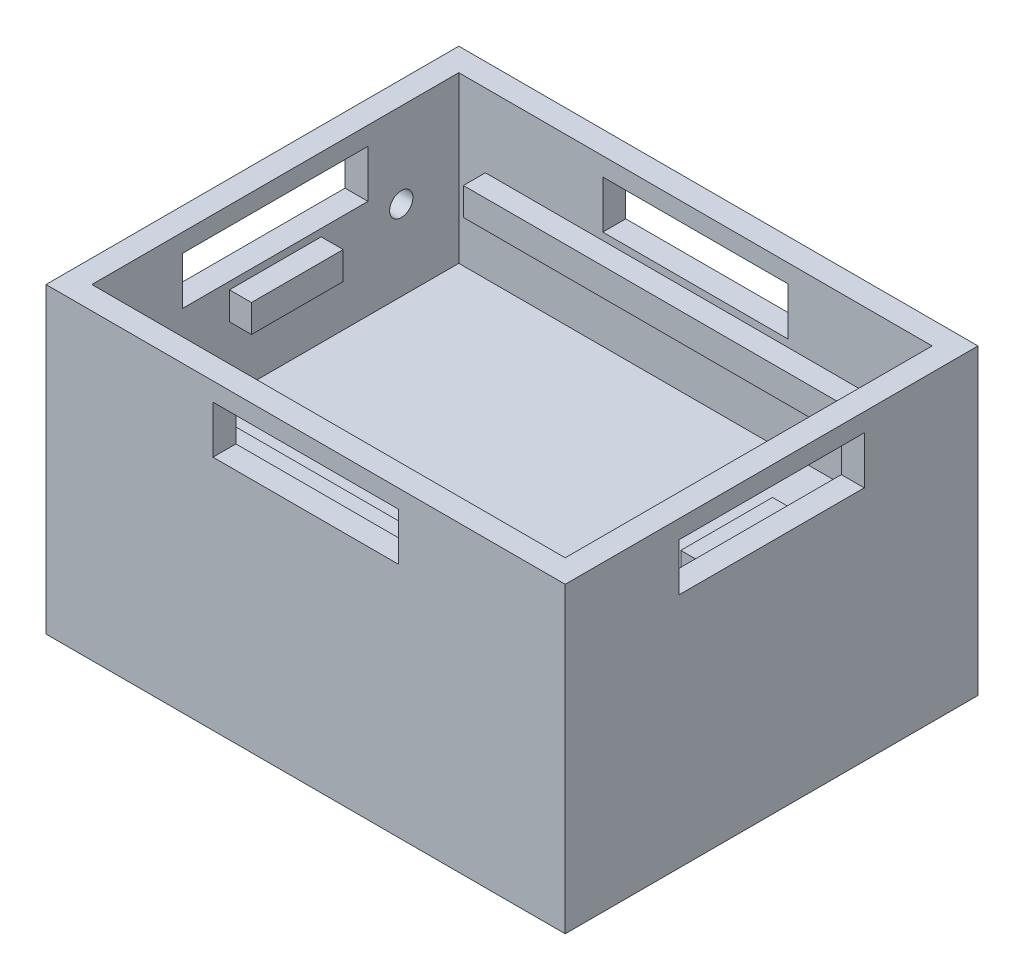
SolidWorks part; units mm, degrees
ref_plane "Front Plane" through (0, 0, 0) normal (0, 0, 1) x (1, 0, 0)
ref_plane "Top Plane" through (0, 0, 0) normal (0, 1, 0) x (1, 0, 0)
ref_plane "Right Plane" through (0, 0, 0) normal (1, 0, 0) x (0, 0, -1)
sketch "Sketch1" plane through (0, 0, 0) normal (0, 1, 0) x (1, 0, 0)
  line L0 (-2.5, 2.5) -> (-2.5, 202.5)
  line L5 (-15, -10) -> (268, -10)
  line L6 (-15, -10) -> (-15, 215)
  line L7 (-15, 215) -> (268, 215)
  line L8 (268, -10) -> (268, 215)
  line L9 (-2.5, 202.5) -> (255.5, 202.5)
  line L10 (255.5, 2.5) -> (255.5, 202.5)
  line L11 (-2.5, 2.5) -> (255.5, 2.5)
  dimension "D1" = 283
  dimension "D2" = 225
  dimension "D3" = 12.5
extrude "Walls" add sketch "Sketch1" along normal blind 90
sketch "Sketch3" plane through (0, 0, 0) normal (0, -1, 0) x (1, 0, 0)
  line L0 (268, -215) -> (-15, -215) construction
  line L1 (268, 10) -> (268, -215) construction
  line L2 (-15, 10) -> (268, 10) construction
  line L3 (-15, -215) -> (-15, 10) construction
  line L4 (268, -215) -> (-15, -215)
  line L5 (268, 10) -> (268, -215)
  line L6 (-15, 10) -> (268, 10)
  line L7 (-15, -215) -> (-15, 10)
extrude "Base" add sketch "Sketch3" along normal blind 12.5
ref_plane "Long_Support_Midplane" through (126.5, 0, 0) normal (1, 0, 0) x (0, 0, -1)
sketch "Sketch4" plane through (126.5, 0, 0) normal (1, 0, 0) x (0, 0, -1)
  line L0 (2.5, 0) -> (2.5, 90)
  line L1 (2.5, 50) -> (14.5, 50)
  line L2 (2.5, 50) -> (2.5, 34.9)
  line L3 (2.5, 34.9) -> (14.5, 34.9)
  line L4 (14.5, 50) -> (14.5, 34.9)
  line L5 (2.5, 0) -> (2.5, 90) construction
  line L6 (202.5, 50) -> (190.5, 50)
  line L7 (202.5, 50) -> (202.5, 34.9)
  line L8 (202.5, 34.9) -> (190.5, 34.9)
  line L9 (190.5, 50) -> (190.5, 34.9)
  line L14 (2.5, 0) -> (202.5, 0)
  line L15 (202.5, 0) -> (202.5, 90)
  line L16 (202.5, 90) -> (2.5, 90)
  line L17 (2.5, 90) -> (2.5, 0)
  line L18 (2.5, 0) -> (202.5, 0) construction
  line L19 (202.5, 0) -> (202.5, 90) construction
  line L20 (202.5, 90) -> (2.5, 90) construction
  line L21 (2.5, 90) -> (2.5, 0) construction
  dimension "D1" = 15.1
  dimension "D2" = 12
  dimension "D4" = 50
extrude "Long_Support" add sketch "Sketch4" along normal mid plane 229
ref_plane "Short_Support_Midplane" through (0, 0, -102.5) normal (0, 0, -1) x (-1, 0, 0)
sketch "Sketch5" plane through (0, 0, -102.5) normal (0, 0, -1) x (-1, 0, 0)
  line L1 (-255.5, 50) -> (-243.5, 50)
  line L2 (-255.5, 50) -> (-255.5, 34.9)
  line L3 (-255.5, 34.9) -> (-243.5, 34.9)
  line L4 (-243.5, 50) -> (-243.5, 34.9)
  line L5 (2.5, 50) -> (-9.5, 50)
  line L6 (2.5, 50) -> (2.5, 34.9)
  line L7 (2.5, 34.9) -> (-9.5, 34.9)
  line L8 (-9.5, 50) -> (-9.5, 34.9)
  line L12 (-255.5, 0) -> (2.5, 0)
  line L13 (2.5, 0) -> (2.5, 90)
  line L14 (2.5, 90) -> (-255.5, 90)
  line L15 (2.5, 0) -> (2.5, 90) construction
  line L16 (-255.5, 0) -> (2.5, 0) construction
  line L20 (-255.5, 90) -> (-255.5, 0)
  line L21 (-255.5, 90) -> (-255.5, 0) construction
  line L22 (2.5, 90) -> (-255.5, 90) construction
  dimension "D4" = 50
  dimension "D2" = 15.1
extrude "Short_Support" add sketch "Sketch5" along normal mid plane 50
sketch "Sketch6" plane through (-2.5, 0, 0) normal (1, 0, 0) x (0, 0, -1)
  line L4 (2.5, 0) -> (202.5, 0)
  line L5 (202.5, 0) -> (202.5, 90)
  line L6 (202.5, 90) -> (2.5, 90)
  line L7 (2.5, 90) -> (2.5, 0)
  line L8 (2.5, 0) -> (202.5, 0) construction
  line L9 (202.5, 0) -> (202.5, 90) construction
  line L10 (202.5, 90) -> (2.5, 90) construction
  line L11 (2.5, 90) -> (2.5, 0) construction
  circle A0 centre (171.15, 43.65) radius 6.35
  dimension "D2" = 12.7
  dimension "D3" = 31.35
  dimension "D4" = 43.65
extrude "Reservoir_Outflow_Tube_Hole" cut sketch "Sketch6" against normal up to next
sketch "Sketch7" plane through (-2.5, 0, 0) normal (1, 0, 0) x (0, 0, -1)
  line L0 (127.5, 50) -> (77.5, 50) construction
  line L1 (52, 54) -> (153, 54)
  line L2 (52, 54) -> (52, 80)
  line L3 (52, 80) -> (153, 80)
  line L4 (153, 54) -> (153, 80)
  line L5 (202.5, 90) -> (2.5, 90) construction
  line L7 (102.5, 80) -> (102.5, 54) construction
  line L8 (102.5, -27.5) -> (102.5, 27.5) construction
  dimension "D1" = 4
  dimension "D2" = 10
  dimension "D3" = 26
  dimension "D4" = 101
extrude "Connector_Port_ShortSide" cut sketch "Sketch7" against normal up to surface (12.5 mm away) up to face at (-15, 43.65, -177.5)
pattern_linear "LPattern1" count 2 spacing 270.5 along (1, 0, 0) of "Connector_Port_ShortSide"
sketch "Sketch8" plane through (0, 0, -2.5) normal (0, 0, 1) x (1, 0, 0)
  line L1 (76, 54) -> (177, 54)
  line L2 (76, 54) -> (76, 80)
  line L3 (76, 80) -> (177, 80)
  line L4 (177, 54) -> (177, 80)
  line L6 (241, 50) -> (12, 50) construction
  line L7 (126.5, 80) -> (126.5, 54) construction
  line L9 (-2.5, 90) -> (255.5, 90) construction
  line L10 (126.5, -28.05) -> (126.5, 28.05) construction
  dimension "D3" = 26
  dimension "D4" = 101
  dimension "D1" = 4
  dimension "D2" = 10
extrude "Connector_Port_LongSide" cut sketch "Sketch8" along normal up to surface (12.5 mm away) contours L4 L3 L2 L1 up to face at (126.5, 38.75, 10)
pattern_linear "LPattern2" count 2 spacing 212.5 along (0, 0, -1) of "Connector_Port_LongSide"
sketch "Sketch9" plane through (0, -12.5, 0) normal (0, -1, 0) x (1, 0, 0)
  line L10 (268, -215) -> (268, 10) construction
  line L11 (-15, -215) -> (268, -215) construction
  line L12 (268, 10) -> (-15, 10) construction
  line L13 (-15, 10) -> (-15, -215) construction
  line L14 (-2.5, -202.5) -> (255.5, -202.5)
  line L15 (255.5, -202.5) -> (255.5, -2.5)
  line L16 (255.5, -2.5) -> (-2.5, -2.5)
  line L17 (-2.5, -2.5) -> (-2.5, -202.5)
  line L18 (-2.5, -202.5) -> (255.5, -202.5)
  line L19 (255.5, -202.5) -> (255.5, -2.5)
  line L20 (255.5, -2.5) -> (-2.5, -2.5)
  line L21 (-2.5, -2.5) -> (-2.5, -202.5)
  line L22 (268, -215) -> (268, 10)
  line L23 (-15, -215) -> (268, -215)
  line L24 (268, 10) -> (-15, 10)
  line L25 (-15, 10) -> (-15, -215)
  dimension "D1" = 12.5
extrude "Lower_Water_Jacket_Walls" add sketch "Sketch9" along normal blind 50
sketch "Sketch11" plane through (0, -62.5, 0) normal (0, -1, 0) x (1, 0, 0)
  line L0 (-15, -215) -> (268, -215) construction
  line L1 (268, -215) -> (268, 10) construction
  line L2 (268, 10) -> (-15, 10) construction
  line L3 (-15, 10) -> (-15, -215) construction
  line L4 (-15, -215) -> (268, -215)
  line L5 (268, -215) -> (268, 10)
  line L6 (268, 10) -> (-15, 10)
  line L7 (-15, 10) -> (-15, -215)
extrude "Lower_Water_Jacket_Bottom" add sketch "Sketch11" along normal blind 12.5
equation "\"Length\"= 283mm"
equation "\"Width\"= 225mm"
equation "\"WallThickness\"= 12.5mm"
equation "\"UpperWaterJacketThickness\"= 28mm"
equation "\"SpacerHeight\"= 80.2mm"
equation "\"PlateLength\"= 252mm"
equation "\"PlateWidth\"= 190mm"
equation "\"PlateHoleDiameter\"= 5.9mm"
equation "\"PlateHoleBottom\"= 2mm"
equation "\"PlateHoleSide\"= 1.55mm"
equation "\"PlateHoleSpacing\"= 3.1mm"
equation "\"PlateThickness\"= 1.55mm"
equation "\"D1@Sketch1\"=\"Length\""
equation "\"D2@Sketch1\"=\"Width\""
equation "\"D3@Sketch1\"=\"WallThickness\""
equation "\"ReservoirBottom\"= 12.5mm"
equation "\"D1@Base\"=\"ReservoirBottom\""
equation "\"ReservoirSupportWidth\"= 12mm"
equation "\"D2@Sketch4\"=\"ReservoirSupportWidth\""
equation "\"ReservoirSupportHeight\"= 15.1mm"
equation "\"D1@Sketch4\"=\"ReservoirSupportHeight\""
equation "\"D1@Sketch5\"=\"ReservoirSupportWidth\""
equation "\"D2@Sketch5\"=\"ReservoirSupportHeight\""
equation "\"ReservoirSupportPlacementHeight\"= 50mm"
equation "\"D4@Sketch5\"=\"ReservoirSupportPlacementHeight\""
equation "\"D4@Sketch4\"=\"ReservoirSupportPlacementHeight\""
equation "\"ReservoirHoleDiameter\"= 12.7mm"
equation "\"D2@Sketch6\"=\"ReservoirHoleDiameter\""
equation "\"ReservoirHoleRight\"= 25mm"
equation "\"D3@Sketch6\"=\"ReservoirHoleRight\"+\"ReservoirHoleDiameter\"/2"
equation "\"ReservoirHoleTop\"= \"ReservoirSupportPlacementHeight\""
equation "\"D4@Sketch6\"=\"ReservoirHoleTop\"-\"ReservoirHoleDiameter\"/2"
equation "\"ReservoirHeight\"= 90mm"
equation "\"D1@Walls\"=\"ReservoirHeight\""
equation "\"ReservoirPortBottom\"= 4mm"
equation "\"D1@Sketch7\"=\"ReservoirPortBottom\""
equation "\"ReservoirPortTop\"= 10mm"
equation "\"D2@Sketch7\"=\"ReservoirPortTop\""
equation "\"ReservoirPortWidth\"= 101mm"
equation "\"D4@Sketch7\"=\"ReservoirPortWidth\""
equation "\"D4@Sketch8\"=\"ReservoirPortWidth\""
equation "\"D1@Sketch8\"=\"ReservoirPortBottom\""
equation "\"D2@Sketch8\"=\"ReservoirPortTop\""
equation "\"D1@Sketch9\"=\"WallThickness\""
equation "\"LowerWaterJacketHeight\"= 50"
equation "\"D1@Lower_Water_Jacket_Walls\" = \"LowerWaterJacketHeight\""
equation "\"LowerWaterJacketBottomThickness\"= \"WallThickness\""
equation "\"D1@Lower_Water_Jacket_Bottom\" = \"LowerWaterJacketBottomThickness\""
